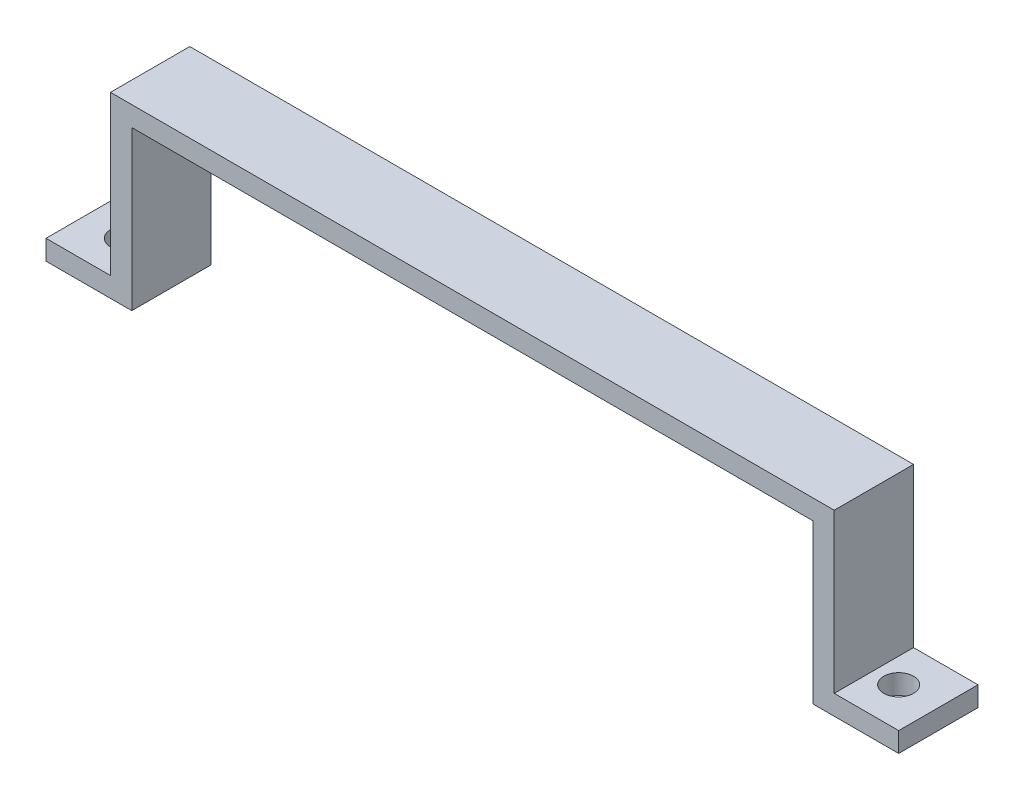
SolidWorks part; units mm, degrees
ref_plane "前视基准面" through (0, 0, 0) normal (0, 0, 1) x (1, 0, 0)
ref_plane "上视基准面" through (0, 0, 0) normal (0, 1, 0) x (1, 0, 0)
ref_plane "右视基准面" through (0, 0, 0) normal (1, 0, 0) x (0, 0, -1)
other "Configuration Table"
sketch "草图1" plane through (0, 0, 0) normal (0, 1, 0) x (1, 0, 0)
  line L0 (34.35, 37) -> (34.35, -78) construction
  line L1 (-36.5, -4) -> (36.5, -4)
  line L2 (-36.5, -4) -> (-36.5, 4)
  line L3 (-36.5, 4) -> (36.5, 4)
  line L4 (36.5, -4) -> (36.5, 4)
  line L5 (-36.5, -4) -> (36.5, 4) construction
  line L6 (-36.5, 4) -> (36.5, -4) construction
  line L23 (-43, 4) -> (-34.35, 4)
  line L24 (-43, 4) -> (-43, -4)
  line L25 (-43, -4) -> (-34.35, -4)
  line L26 (-34.35, 4) -> (-34.35, -4)
  line L27 (34.35, -4) -> (43, -4)
  line L28 (34.35, -4) -> (34.35, 4)
  line L29 (34.35, 4) -> (43, 4)
  line L30 (43, -4) -> (43, 4)
  line L31 (-34.35, 37) -> (-34.35, -78) construction
  circle A0 centre (-39, 0) radius 1.5
  circle A1 centre (39, 0) radius 1.5
  point P0 (0, 0)
  point P21 (-43, 0)
  dimension "D1" = 73
  dimension "D2" = 8
  dimension "D3" = 8.65
  dimension "D4" = 4
  dimension "D5" = 3
  dimension "D6" = 4
extrude "凸台-拉伸1" add sketch "草图1" along normal blind 2 contours L1 L4 L3 L2
extrude "凸台-拉伸2" add sketch "草图1<15>" against normal blind 16 contours L26 L3 L2 L1 | L28 L1 L4 L3 region at (-35.425, 0, 0) region at (35.425, 0, 0)
sketch "草图1<15>" plane through (0, 0, 0) normal (0, 1, 0) x (1, 0, 0) same geometry as "草图1"
extrude "凸台-拉伸3" add sketch "草图1<16>" along normal blind 2 from surface contours L24 L25 L2 L23 | L27 L30 L29 L4 region at (-39.75, 0, 3.8969) region at (36.6031, 0, 0) starting at face at (-35.425, -16, 0)
sketch "草图1<16>" plane through (0, 0, 0) normal (0, 1, 0) x (1, 0, 0) same geometry as "草图1"
